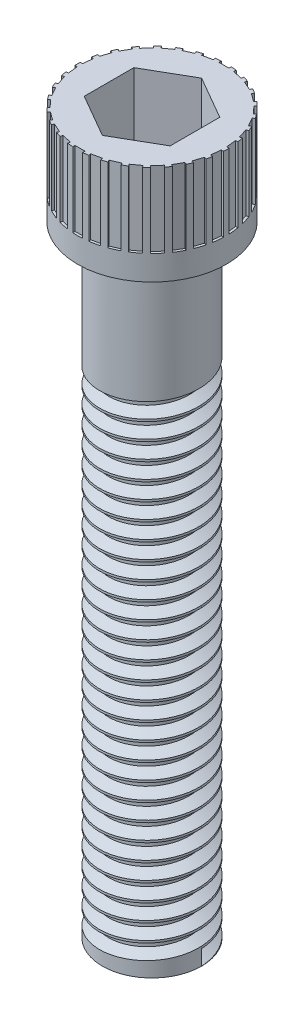
SolidWorks part; units mm, degrees
ref_plane "Front Plane" through (0, 0, 0) normal (0, 0, 1) x (1, 0, 0)
ref_plane "Top Plane" through (0, 0, 0) normal (0, 1, 0) x (1, 0, 0)
ref_plane "Right Plane" through (0, 0, 0) normal (1, 0, 0) x (0, 0, -1)
sketch "Sketch1" plane through (0, 0, 0) normal (0, 1, 0) x (1, 0, 0)
  circle A0 centre (0, 0) radius 2
  dimension "D1" = 4
extrude "Boss-Extrude1" add sketch "Sketch1" along normal blind 25
sketch "Sketch2" plane through (0, 25, 0) normal (0, 1, 0) x (1, 0, 0)
  circle A0 centre (0, 0) radius 3
  dimension "D1" = 6
extrude "Boss-Extrude2" add sketch "Sketch2" along normal blind 4
sketch "Sketch3" plane through (0, 29, 0) normal (0, 1, 0) x (1, 0, 0)
  line L1 (0, 2) -> (-1.7321, 1)
  line L2 (-1.7321, 1) -> (-1.7321, -1)
  line L3 (-1.7321, -1) -> (0, -2)
  line L4 (0, -2) -> (1.7321, -1)
  line L5 (1.7321, -1) -> (1.7321, 1)
  line L6 (1.7321, 1) -> (0, 2)
  circle A2 centre (0, 0) radius 1.7321 construction
  circle A3 centre (0, 0) radius 2
  circle A4 centre (0, 0) radius 2
  dimension "D1" = 1
extrude "Cut-Extrude1" cut sketch "Sketch3" against normal blind 3 contours L5 L6 L1 L2 L3 L4 region at (0, 29, 0)
sketch "Sketch4" plane through (0, 29, 0) normal (0, 1, 0) x (1, 0, 0)
  line L0 (0.4489, 3.0738) -> (0.4073, 2.8782)
  line L1 (-0.2, 3.1) -> (0.2, 3.1)
  line L2 (-0.2, 3.1) -> (-0.2, 2.9)
  line L3 (-0.2, 2.9) -> (0.2, 2.9)
  line L4 (0.2, 3.1) -> (0.2, 2.9)
  line L5 (0, 2.9) -> (0, 3.1) construction
  line L6 (-0.2, 3) -> (0.2, 3) construction
  line L7 (0.4489, 3.0738) -> (0.8402, 2.9907)
  line L8 (0.8402, 2.9907) -> (0.7986, 2.795)
  line L9 (0.4073, 2.8782) -> (0.7986, 2.795)
  line L10 (1.0782, 2.9133) -> (0.9968, 2.7306)
  line L11 (1.0782, 2.9133) -> (1.4436, 2.7506)
  line L12 (1.4436, 2.7506) -> (1.3622, 2.5679)
  line L13 (0.9968, 2.7306) -> (1.3622, 2.5679)
  line L14 (1.6603, 2.6255) -> (1.5428, 2.4637)
  line L15 (1.6603, 2.6255) -> (1.9839, 2.3904)
  line L16 (1.9839, 2.3904) -> (1.8664, 2.2286)
  line L17 (1.5428, 2.4637) -> (1.8664, 2.2286)
  line L18 (2.1699, 2.2229) -> (2.0213, 2.0891)
  line L19 (2.1699, 2.2229) -> (2.4376, 1.9257)
  line L20 (2.4376, 1.9257) -> (2.2889, 1.7918)
  line L21 (2.0213, 2.0891) -> (2.2889, 1.7918)
  line L22 (2.5847, 1.7232) -> (2.4115, 1.6232)
  line L23 (2.5847, 1.7232) -> (2.7847, 1.3768)
  line L24 (2.7847, 1.3768) -> (2.6115, 1.2768)
  line L25 (2.4115, 1.6232) -> (2.6115, 1.2768)
  line L26 (2.8865, 1.1482) -> (2.6963, 1.0864)
  line L27 (2.8865, 1.1482) -> (3.0101, 0.7677)
  line L28 (3.0101, 0.7677) -> (2.8199, 0.7059)
  line L29 (2.6963, 1.0864) -> (2.8199, 0.7059)
  line L30 (3.0621, 0.5229) -> (2.8632, 0.502)
  line L31 (3.0621, 0.5229) -> (3.1039, 0.1251)
  line L32 (3.1039, 0.1251) -> (2.905, 0.1042)
  line L33 (2.8632, 0.502) -> (2.905, 0.1042)
  line L34 (3.1039, -0.1251) -> (2.905, -0.1042)
  line L35 (3.1039, -0.1251) -> (3.0621, -0.5229)
  line L36 (3.0621, -0.5229) -> (2.8632, -0.502)
  line L37 (2.905, -0.1042) -> (2.8632, -0.502)
  line L38 (3.0101, -0.7677) -> (2.8199, -0.7059)
  line L39 (3.0101, -0.7677) -> (2.8865, -1.1482)
  line L40 (2.8865, -1.1482) -> (2.6963, -1.0864)
  line L41 (2.8199, -0.7059) -> (2.6963, -1.0864)
  line L42 (2.7847, -1.3768) -> (2.6115, -1.2768)
  line L43 (2.7847, -1.3768) -> (2.5847, -1.7232)
  line L44 (2.5847, -1.7232) -> (2.4115, -1.6232)
  line L45 (2.6115, -1.2768) -> (2.4115, -1.6232)
  line L46 (2.4376, -1.9257) -> (2.2889, -1.7918)
  line L47 (2.4376, -1.9257) -> (2.1699, -2.2229)
  line L48 (2.1699, -2.2229) -> (2.0213, -2.0891)
  line L49 (2.2889, -1.7918) -> (2.0213, -2.0891)
  line L50 (1.9839, -2.3904) -> (1.8664, -2.2286)
  line L51 (1.9839, -2.3904) -> (1.6603, -2.6255)
  line L52 (1.6603, -2.6255) -> (1.5428, -2.4637)
  line L53 (1.8664, -2.2286) -> (1.5428, -2.4637)
  line L54 (1.4436, -2.7506) -> (1.3622, -2.5679)
  line L55 (1.4436, -2.7506) -> (1.0782, -2.9133)
  line L56 (1.0782, -2.9133) -> (0.9968, -2.7306)
  line L57 (1.3622, -2.5679) -> (0.9968, -2.7306)
  line L58 (0.8402, -2.9907) -> (0.7986, -2.795)
  line L59 (0.8402, -2.9907) -> (0.4489, -3.0738)
  line L60 (0.4489, -3.0738) -> (0.4073, -2.8782)
  line L61 (0.7986, -2.795) -> (0.4073, -2.8782)
  line L62 (0.2, -3.1) -> (0.2, -2.9)
  line L63 (0.2, -3.1) -> (-0.2, -3.1)
  line L64 (-0.2, -3.1) -> (-0.2, -2.9)
  line L65 (0.2, -2.9) -> (-0.2, -2.9)
  line L66 (-0.4489, -3.0738) -> (-0.4073, -2.8782)
  line L67 (-0.4489, -3.0738) -> (-0.8402, -2.9907)
  line L68 (-0.8402, -2.9907) -> (-0.7986, -2.795)
  line L69 (-0.4073, -2.8782) -> (-0.7986, -2.795)
  line L70 (-1.0782, -2.9133) -> (-0.9968, -2.7306)
  line L71 (-1.0782, -2.9133) -> (-1.4436, -2.7506)
  line L72 (-1.4436, -2.7506) -> (-1.3622, -2.5679)
  line L73 (-0.9968, -2.7306) -> (-1.3622, -2.5679)
  line L74 (-1.6603, -2.6255) -> (-1.5428, -2.4637)
  line L75 (-1.6603, -2.6255) -> (-1.9839, -2.3904)
  line L76 (-1.9839, -2.3904) -> (-1.8664, -2.2286)
  line L77 (-1.5428, -2.4637) -> (-1.8664, -2.2286)
  line L78 (-2.1699, -2.2229) -> (-2.0213, -2.0891)
  line L79 (-2.1699, -2.2229) -> (-2.4376, -1.9257)
  line L80 (-2.4376, -1.9257) -> (-2.2889, -1.7918)
  line L81 (-2.0213, -2.0891) -> (-2.2889, -1.7918)
  line L82 (-2.5847, -1.7232) -> (-2.4115, -1.6232)
  line L83 (-2.5847, -1.7232) -> (-2.7847, -1.3768)
  line L84 (-2.7847, -1.3768) -> (-2.6115, -1.2768)
  line L85 (-2.4115, -1.6232) -> (-2.6115, -1.2768)
  line L86 (-2.8865, -1.1482) -> (-2.6963, -1.0864)
  line L87 (-2.8865, -1.1482) -> (-3.0101, -0.7677)
  line L88 (-3.0101, -0.7677) -> (-2.8199, -0.7059)
  line L89 (-2.6963, -1.0864) -> (-2.8199, -0.7059)
  line L90 (-3.0621, -0.5229) -> (-2.8632, -0.502)
  line L91 (-3.0621, -0.5229) -> (-3.1039, -0.1251)
  line L92 (-3.1039, -0.1251) -> (-2.905, -0.1042)
  line L93 (-2.8632, -0.502) -> (-2.905, -0.1042)
  line L94 (-3.1039, 0.1251) -> (-2.905, 0.1042)
  line L95 (-3.1039, 0.1251) -> (-3.0621, 0.5229)
  line L96 (-3.0621, 0.5229) -> (-2.8632, 0.502)
  line L97 (-2.905, 0.1042) -> (-2.8632, 0.502)
  line L98 (-3.0101, 0.7677) -> (-2.8199, 0.7059)
  line L99 (-3.0101, 0.7677) -> (-2.8865, 1.1482)
  line L100 (-2.8865, 1.1482) -> (-2.6963, 1.0864)
  line L101 (-2.8199, 0.7059) -> (-2.6963, 1.0864)
  line L102 (-2.7847, 1.3768) -> (-2.6115, 1.2768)
  line L103 (-2.7847, 1.3768) -> (-2.5847, 1.7232)
  line L104 (-2.5847, 1.7232) -> (-2.4115, 1.6232)
  line L105 (-2.6115, 1.2768) -> (-2.4115, 1.6232)
  line L106 (-2.4376, 1.9257) -> (-2.2889, 1.7918)
  line L107 (-2.4376, 1.9257) -> (-2.1699, 2.2229)
  line L108 (-2.1699, 2.2229) -> (-2.0213, 2.0891)
  line L109 (-2.2889, 1.7918) -> (-2.0213, 2.0891)
  line L110 (-1.9839, 2.3904) -> (-1.8664, 2.2286)
  line L111 (-1.9839, 2.3904) -> (-1.6603, 2.6255)
  line L112 (-1.6603, 2.6255) -> (-1.5428, 2.4637)
  line L113 (-1.8664, 2.2286) -> (-1.5428, 2.4637)
  line L114 (-1.4436, 2.7506) -> (-1.3622, 2.5679)
  line L115 (-1.4436, 2.7506) -> (-1.0782, 2.9133)
  line L116 (-1.0782, 2.9133) -> (-0.9968, 2.7306)
  line L117 (-1.3622, 2.5679) -> (-0.9968, 2.7306)
  line L118 (-0.8402, 2.9907) -> (-0.7986, 2.795)
  line L119 (-0.8402, 2.9907) -> (-0.4489, 3.0738)
  line L120 (-0.4489, 3.0738) -> (-0.4073, 2.8782)
  line L121 (-0.7986, 2.795) -> (-0.4073, 2.8782)
  circle A0 centre (0, 0) radius 3 construction
  point P0 (0, 3)
  point P125 (0, 0)
  dimension "D1" = 0.4
  dimension "D2" = 0.2
  dimension "D3" = 30
extrude "Cut-Extrude2" cut sketch "Sketch4" against normal blind 3
thread "Thread1" pitch 0.7 method cut profile "Thread Profile1" start angle 0, offset 0, length 20, pitch 0.7, diameter 4
ref_plane "Plane1" through (2, 0, 0) normal (0, 0, 1) x (1, 0, 0)
sketch "Thread Profile1" plane through (2, 0, 0) normal (0, 0, 1) x (1, 0, 0)
  line L0 (0, 0) -> (0, 0.7) construction
  line L11 (0, 0) -> (0, 0.6125)
  line L12 (0, 0.6125) -> (-0.3789, 0.3937)
  line L13 (-0.3789, 0.3937) -> (-0.3789, 0.2187)
  line L15 (-0.3789, 0.2187) -> (0, 0)
  line L17 (-0.3789, 0.3062) -> (0, 0.3062) construction
  point P2 (0, 0)
  dimension "Pitch" = 0.7
  dimension "Profile_Angle" = 60
  dimension "Profile_Land" = 0.175
  dimension "Profile_Height" = 0.3789
